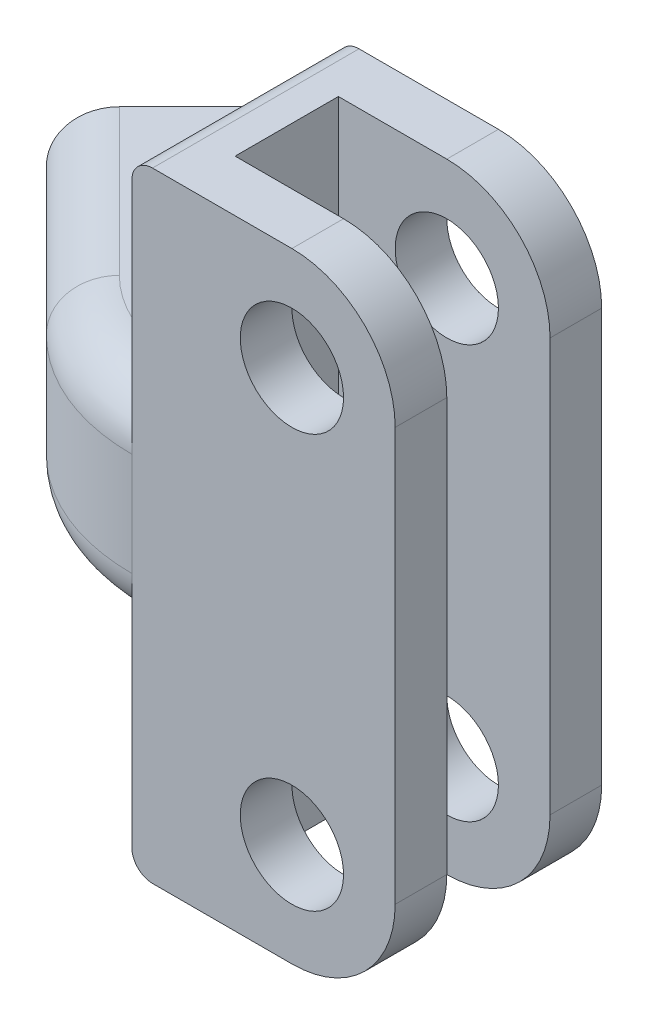
SolidWorks part; units mm, degrees
ref_plane "Front Plane" through (0, 0, 0) normal (0, 0, 1) x (1, 0, 0)
ref_plane "Top Plane" through (0, 0, 0) normal (0, 1, 0) x (1, 0, 0)
ref_plane "Right Plane" through (0, 0, 0) normal (1, 0, 0) x (0, 0, -1)
ref_axis "X" through (-88.99, 0, 0) along (1, 0, 0)
ref_axis "Y" through (0, 55, 0) along (0, -1, 0)
ref_axis "Z" through (0, 0, -88.99) along (0, 0, 1)
sketch "Sketch1" plane through (0, 0, 0) normal (0, 0, 1) x (1, 0, 0)
  line L0 (0, 20) -> (0, -20) construction
  line L1 (-10.5, 30) -> (0, 30)
  line L2 (10, 20) -> (10, -20)
  line L3 (0, -30) -> (-10.5, -30)
  line L4 (-10.5, 30) -> (-10.5, -30)
  line L5 (-10.5, 30) -> (-15.5, 30)
  line L6 (-15.5, 30) -> (-15.5, -30)
  line L7 (-15.5, -30) -> (-10.5, -30)
  circle A0 centre (0, 20) radius 5
  circle A1 centre (0, -20) radius 5
  arc A2 (0, 30) -> (10, 20) centre (0, 20) cw
  arc A3 (10, -20) -> (0, -30) centre (0, -20) cw
  point P4 (0, 0)
  dimension "D1" = 40
  dimension "D2" = 10
  dimension "D3" = 5
  dimension "D4" = 10.5
  dimension "D5" = 5
extrude "Boss-Extrude1" add sketch "Sketch1" along normal mid plane 10 contours L6 L7 L4 L5 region at (-13, 0, 0)
extrude "Boss-Extrude2" add sketch "Sketch1<3>" along normal blind 5 from surface contours L6 L7 L4 L5 | A3 L2 A2 L1 L4 L3 A0 A1 region at (-0.6222, 0, 0) region at (-13, 0, 0) starting at face at (-13, 0, 5)
sketch "Sketch1<3>" plane through (0, 0, 0) normal (0, 0, 1) x (1, 0, 0) same geometry as "Sketch1"
extrude "Boss-Extrude3" add sketch "Sketch1<4>" against normal blind 5 from surface contours A3 L2 A2 L1 L4 L3 A0 A1 | L6 L7 L4 L5 region at (-0.6222, 0, 0) region at (-13, 0, 0) starting at face at (-13, 0, -5)
sketch "Sketch1<4>" plane through (0, 0, 0) normal (0, 0, 1) x (1, 0, 0) same geometry as "Sketch1"
sketch "Sketch3" plane through (0, 0, 0) normal (0, 1, 0) x (1, 0, 0)
  line L0 (-15.5, -10) -> (-15.5, 10) construction
  line L1 (-15.5, -10) -> (-15.5, 10)
  line L2 (-15.5, -10) -> (-29.6421, -24.1421)
  line L3 (-29.6421, -24.1421) -> (-43.7843, -10)
  line L5 (-29.6421, 4.1421) -> (-43.7843, -10)
  line L6 (-15.5, 10) -> (-12.0739, 10) construction
  arc A0 (-15.5, 10) -> (-29.6421, 4.1421) centre (-15.5, -10) ccw
  dimension "D1" = 20
  dimension "D2" = 20
  dimension "D3" = 45
extrude "Boss-Extrude4" add sketch "Sketch3" along normal mid plane 20
fillet "Fillet3" radius 5 6 edges at (-23.1537, -10, -8.4776) (-23.1537, 10, -8.4776) (-22.5711, -10, 17.0711) (-22.5711, 10, 17.0711) (-36.7132, -10, 2.9289) (-36.7132, 10, 2.9289)
fillet "Fillet2" radius 2 2 edges at (-15.5, -30, 0) (-15.5, 30, 0)
sketch "Sketch4" plane through (-26.8921, 0, 26.8921) normal (-0.7071, 0, 0.7071) x (0.7071, 0, 0.7071)
  line L4 (-23.8891, 0) -> (-3.8891, 0) construction
  line L8 (-18.8891, -10) -> (-8.8891, -10)
  line L9 (-3.8891, -5) -> (-3.8891, 5)
  line L10 (-8.8891, 10) -> (-18.8891, 10)
  line L11 (-23.8891, 5) -> (-23.8891, -5)
  line L12 (-18.8891, -10) -> (-8.8891, -10)
  line L13 (-3.8891, -5) -> (-3.8891, 5)
  line L14 (-8.8891, 10) -> (-18.8891, 10)
  line L15 (-23.8891, 5) -> (-23.8891, -5)
  circle A4 centre (-13.8891, 0) radius 7.5
  arc A8 (-8.8891, -10) -> (-3.8891, -5) centre (-8.8891, -5) ccw
  arc A9 (-3.8891, 5) -> (-8.8891, 10) centre (-8.8891, 5) ccw
  arc A10 (-18.8891, 10) -> (-23.8891, 5) centre (-18.8891, 5) ccw
  arc A11 (-23.8891, -5) -> (-18.8891, -10) centre (-18.8891, -5) ccw
  arc A12 (-8.8891, -10) -> (-3.8891, -5) centre (-8.8891, -5) ccw
  arc A13 (-3.8891, 5) -> (-8.8891, 10) centre (-8.8891, 5) ccw
  arc A14 (-18.8891, 10) -> (-23.8891, 5) centre (-18.8891, 5) ccw
  arc A15 (-23.8891, -5) -> (-18.8891, -10) centre (-18.8891, -5) ccw
  dimension "D2" = 15
  dimension "D1" = 0
extrude "Cut-Extrude1" cut sketch "Sketch4" against normal blind 15 contours A4 L4 | L4 A4 region at (-36.7132, -3.1831, 17.0711) region at (-36.7132, 3.1831, 17.0711)
mirror "Mirror1" about plane through (0, 0, 0) normal (0, 0, 1) of bodies 105
delete or keep bodies "Body-Delete/Keep 1" type delete bodies bodies 105
